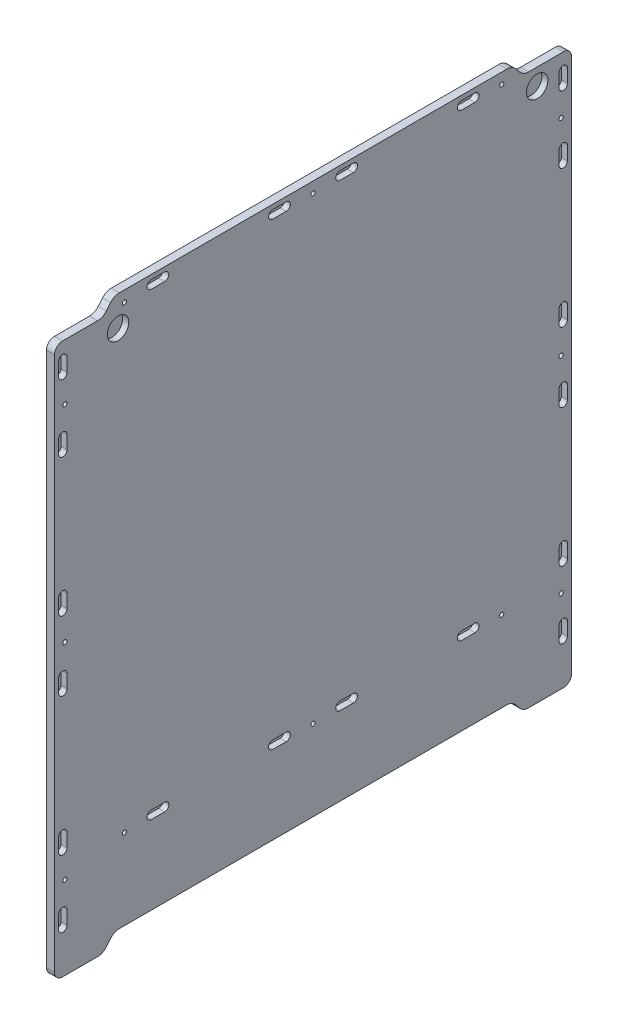
SolidWorks part; units mm, degrees
ref_plane "Alzado" through (0, 0, 0) normal (0, 0, 1) x (1, 0, 0)
ref_plane "Planta" through (0, 0, 0) normal (0, 1, 0) x (1, 0, 0)
ref_plane "Vista lateral" through (0, 0, 0) normal (1, 0, 0) x (0, 0, -1)
sketch "Croquis1" plane through (0, 0, 0) normal (1, 0, 0) x (0, 0, -1)
  line L0 (-15.4032, 213.9092) -> (-15.4032, -196.0905) construction
  line L1 (138.549, -203.0545) -> (135.2533, -199.1268)
  line L2 (171.0968, -206.0908) -> (145.0604, -206.0908)
  line L3 (177.0968, 198.0069) -> (177.0968, -200.0908)
  line L4 (145.0968, 204.0069) -> (171.0968, 204.0069)
  line L5 (-159.667, 213.9092) -> (128.8605, 213.9092)
  line L6 (-166.1784, 210.8729) -> (-169.3918, 207.0432)
  line L7 (-175.9032, 204.0069) -> (-201.9032, 204.0069)
  line L8 (-207.9032, 198.0069) -> (-207.9032, -200.0908)
  line L9 (-201.9032, -206.0908) -> (-175.8668, -206.0908)
  line L10 (-169.3555, -203.0545) -> (-166.0597, -199.1268)
  line L11 (-159.5483, -196.0905) -> (128.7419, -196.0905)
  line L12 (135.3719, 210.8729) -> (138.5854, 207.0432)
  line L21 (-207.9032, 8.9094) -> (177.0968, 8.9094) construction
  arc A0 (128.7419, -196.0905) -> (135.2533, -199.1268) centre (128.7419, -204.5905) cw
  arc A1 (145.0604, -206.0908) -> (138.549, -203.0545) centre (145.0604, -197.5908) cw
  arc A2 (177.0968, -200.0908) -> (171.0968, -206.0908) centre (171.0968, -200.0908) cw
  arc A3 (171.0968, 204.0069) -> (177.0968, 198.0069) centre (171.0968, 198.0069) cw
  arc A4 (145.0968, 204.0069) -> (138.5854, 207.0432) centre (145.0968, 212.5069) cw
  arc A5 (-159.667, 213.9092) -> (-166.1784, 210.8729) centre (-159.667, 205.4092) ccw
  arc A6 (-175.9032, 204.0069) -> (-169.3918, 207.0432) centre (-175.9032, 212.5069) ccw
  arc A7 (-201.9032, 204.0069) -> (-207.9032, 198.0069) centre (-201.9032, 198.0069) ccw
  arc A8 (-207.9032, -200.0908) -> (-201.9032, -206.0908) centre (-201.9032, -200.0908) ccw
  arc A9 (-175.8668, -206.0908) -> (-169.3555, -203.0545) centre (-175.8668, -197.5908) ccw
  arc A10 (-159.5483, -196.0905) -> (-166.0597, -199.1268) centre (-159.5483, -204.5905) ccw
  arc A11 (128.8605, 213.9092) -> (135.3719, 210.8729) centre (128.8605, 205.4092) cw
  circle A12 centre (151.4968, 191.5069) radius 4.25
  circle A13 centre (-160.6032, 191.5069) radius 4.25
  circle A22 centre (-15.4032, 205.9092) radius 1.55
  circle A23 centre (125.0968, 205.9092) radius 1.55
  circle A24 centre (-155.9032, 205.9092) radius 1.55
  circle A25 centre (-15.4032, -136.0908) radius 1.55
  circle A26 centre (125.0968, -136.0908) radius 1.55
  circle A27 centre (-155.9032, -136.0908) radius 1.55
  circle A28 centre (-200.1532, 162.2069) radius 1.6
  circle A29 centre (-200.1532, 8.9094) radius 1.6
  circle A30 centre (-200.1532, -144.3882) radius 1.6
  circle A31 centre (169.3468, -144.3882) radius 1.6
  circle A32 centre (169.3468, 8.9094) radius 1.6
  circle A33 centre (169.3468, 162.2069) radius 1.6
  point P42 (-15.4032, 8.9094)
  dimension "D3" = 15.9023
  dimension "D5" = 385
  dimension "D6" = 25.6
  dimension "D8" = 47.3
  dimension "D4" = 8.5
  dimension "D12" = 41.8
  dimension "D13" = 52
  dimension "D14" = 52
  dimension "D15" = 7.75
  dimension "D16" = 52
  dimension "D17" = 52
  dimension "D22" = 6
  dimension "D23" = 6
  dimension "D25" = 8.5
  dimension "D26" = 8.5
  dimension "D27" = 50
  dimension "D29" = 8.5
  dimension "D30" = 8.5
  dimension "D33" = 3.2
  dimension "D34" = 3.2
  dimension "D18" = 7.75
  dimension "D21" = 10.0003
  dimension "D28" = 32.0364
  dimension "D31" = 32
  dimension "D32" = 50
  dimension "Ancho_panel" = 385
  dimension "Alto_panel" = 420
extrude "Saliente-Extruir1" add sketch "Croquis1" along normal blind 6
sketch "Croquis3" plane through (6, 0, 0) normal (1, 0, 0) x (0, 0, -1)
  line L0 (-15.4032, 213.9092) -> (-15.4032, -196.0905) construction
  line L1 (128.8605, 213.9092) -> (-159.667, 213.9092) construction
  line L2 (-159.5483, -196.0905) -> (128.7419, -196.0905) construction
  line L5 (-198.6032, 192.2069) -> (-198.6032, 182.2069)
  line L6 (-204.8032, 192.2069) -> (-204.8032, 182.2069)
  line L7 (-175.9032, 204.0069) -> (-201.9032, 204.0069) construction
  line L8 (-207.9032, 198.0069) -> (-207.9032, -200.0908) construction
  line L9 (-198.6032, 142.2069) -> (-198.6032, 132.2069)
  line L10 (-204.8032, 142.2069) -> (-204.8032, 132.2069)
  line L11 (177.0968, 8.9094) -> (-207.9032, 8.9094) construction
  line L12 (177.0968, -200.0908) -> (177.0968, 198.0069) construction
  line L13 (-198.6032, -124.3882) -> (-198.6032, -114.3882)
  line L14 (-204.8032, -124.3882) -> (-204.8032, -114.3882)
  line L15 (-204.8032, -174.3882) -> (-204.8032, -164.3882)
  line L16 (-198.6032, -174.3882) -> (-198.6032, -164.3882)
  line L17 (-15.4032, 8.9094) -> (-15.4032, 213.9092) construction
  line L19 (-201.7032, 179.1069) -> (-201.7032, 145.3069) construction
  line L20 (-198.6032, 39.7671) -> (-198.6032, 29.7671)
  line L21 (-204.8032, 39.7671) -> (-204.8032, 29.7671)
  line L22 (-198.6032, -11.9484) -> (-198.6032, -21.9484)
  line L23 (-204.8032, -11.9484) -> (-204.8032, -21.9484)
  line L24 (-201.7032, 26.6671) -> (-201.7032, -8.8484) construction
  line L25 (167.7968, -174.3882) -> (167.7968, -164.3882)
  line L26 (173.9968, -174.3882) -> (173.9968, -164.3882)
  line L27 (173.9968, -124.3882) -> (173.9968, -114.3882)
  line L28 (167.7968, -124.3882) -> (167.7968, -114.3882)
  line L29 (173.9968, -11.9484) -> (173.9968, -21.9484)
  line L30 (167.7968, -11.9484) -> (167.7968, -21.9484)
  line L31 (173.9968, 39.7671) -> (173.9968, 29.7671)
  line L32 (-45.4032, 210.5092) -> (-35.4032, 210.5092)
  line L33 (-45.4032, 204.3092) -> (-35.4032, 204.3092)
  line L34 (-135.9032, 210.5092) -> (-125.9032, 210.5092)
  line L35 (-135.9032, 204.3092) -> (-125.9032, 204.3092)
  line L36 (167.7968, 39.7671) -> (167.7968, 29.7671)
  line L37 (105.0968, 204.3092) -> (95.0968, 204.3092)
  line L38 (105.0968, 210.5092) -> (95.0968, 210.5092)
  line L39 (14.5968, 204.3092) -> (4.5968, 204.3092)
  line L40 (14.5968, 210.5092) -> (4.5968, 210.5092)
  line L41 (-135.9032, -131.4908) -> (-125.9032, -131.4908)
  line L42 (-135.9032, -137.6908) -> (-125.9032, -137.6908)
  line L43 (-45.4032, -131.4908) -> (-35.4032, -131.4908)
  line L44 (-45.4032, -137.6908) -> (-35.4032, -137.6908)
  line L45 (14.5968, -131.4908) -> (4.5968, -131.4908)
  line L46 (14.5968, -137.6908) -> (4.5968, -137.6908)
  line L47 (105.0968, -131.4908) -> (95.0968, -131.4908)
  line L48 (105.0968, -137.6908) -> (95.0968, -137.6908)
  line L49 (-135.9032, 210.5092) -> (-135.9032, -131.4908) construction
  line L50 (173.9968, 142.2069) -> (173.9968, 132.2069)
  line L51 (167.7968, 142.2069) -> (167.7968, 132.2069)
  line L52 (173.9968, 192.2069) -> (173.9968, 182.2069)
  line L53 (167.7968, 192.2069) -> (167.7968, 182.2069)
  circle A0 centre (-160.6032, 191.5069) radius 8
  circle A1 centre (151.4968, 191.5069) radius 8
  arc A4 (-198.6032, 192.2069) -> (-204.8032, 192.2069) centre (-201.7032, 192.2069) ccw
  arc A5 (-204.8032, 182.2069) -> (-198.6032, 182.2069) centre (-201.7032, 182.2069) ccw
  arc A6 (-198.6032, 142.2069) -> (-204.8032, 142.2069) centre (-201.7032, 142.2069) ccw
  arc A7 (-204.8032, 132.2069) -> (-198.6032, 132.2069) centre (-201.7032, 132.2069) ccw
  arc A8 (-204.8032, -114.3882) -> (-198.6032, -114.3882) centre (-201.7032, -114.3882) cw
  arc A9 (-198.6032, -124.3882) -> (-204.8032, -124.3882) centre (-201.7032, -124.3882) cw
  arc A10 (-204.8032, -164.3882) -> (-198.6032, -164.3882) centre (-201.7032, -164.3882) cw
  arc A11 (-198.6032, -174.3882) -> (-204.8032, -174.3882) centre (-201.7032, -174.3882) cw
  arc A12 (-198.6032, 39.7671) -> (-204.8032, 39.7671) centre (-201.7032, 39.7671) ccw
  arc A13 (-204.8032, 29.7671) -> (-198.6032, 29.7671) centre (-201.7032, 29.7671) ccw
  arc A14 (-198.6032, -11.9484) -> (-204.8032, -11.9484) centre (-201.7032, -11.9484) ccw
  arc A15 (-204.8032, -21.9484) -> (-198.6032, -21.9484) centre (-201.7032, -21.9484) ccw
  arc A16 (167.7968, -174.3882) -> (173.9968, -174.3882) centre (170.8968, -174.3882) ccw
  arc A17 (173.9968, -164.3882) -> (167.7968, -164.3882) centre (170.8968, -164.3882) ccw
  arc A18 (167.7968, -124.3882) -> (173.9968, -124.3882) centre (170.8968, -124.3882) ccw
  arc A19 (173.9968, -114.3882) -> (167.7968, -114.3882) centre (170.8968, -114.3882) ccw
  arc A20 (173.9968, -21.9484) -> (167.7968, -21.9484) centre (170.8968, -21.9484) cw
  arc A21 (167.7968, -11.9484) -> (173.9968, -11.9484) centre (170.8968, -11.9484) cw
  arc A22 (173.9968, 29.7671) -> (167.7968, 29.7671) centre (170.8968, 29.7671) cw
  arc A23 (167.7968, 39.7671) -> (173.9968, 39.7671) centre (170.8968, 39.7671) cw
  arc A24 (173.9968, 132.2069) -> (167.7968, 132.2069) centre (170.8968, 132.2069) cw
  arc A25 (167.7968, 142.2069) -> (173.9968, 142.2069) centre (170.8968, 142.2069) cw
  arc A26 (173.9968, 182.2069) -> (167.7968, 182.2069) centre (170.8968, 182.2069) cw
  arc A27 (167.7968, 192.2069) -> (173.9968, 192.2069) centre (170.8968, 192.2069) cw
  arc A28 (-35.4032, 204.3092) -> (-35.4032, 210.5092) centre (-35.4032, 207.4092) ccw
  arc A29 (-45.4032, 210.5092) -> (-45.4032, 204.3092) centre (-45.4032, 207.4092) ccw
  arc A30 (-125.9032, 204.3092) -> (-125.9032, 210.5092) centre (-125.9032, 207.4092) ccw
  arc A31 (-135.9032, 210.5092) -> (-135.9032, 204.3092) centre (-135.9032, 207.4092) ccw
  arc A32 (105.0968, 210.5092) -> (105.0968, 204.3092) centre (105.0968, 207.4092) cw
  arc A33 (95.0968, 204.3092) -> (95.0968, 210.5092) centre (95.0968, 207.4092) cw
  arc A34 (14.5968, 210.5092) -> (14.5968, 204.3092) centre (14.5968, 207.4092) cw
  arc A35 (4.5968, 204.3092) -> (4.5968, 210.5092) centre (4.5968, 207.4092) cw
  arc A36 (-125.9032, -137.6908) -> (-125.9032, -131.4908) centre (-125.9032, -134.5908) ccw
  arc A37 (-135.9032, -131.4908) -> (-135.9032, -137.6908) centre (-135.9032, -134.5908) ccw
  arc A38 (-35.4032, -137.6908) -> (-35.4032, -131.4908) centre (-35.4032, -134.5908) ccw
  arc A39 (-45.4032, -131.4908) -> (-45.4032, -137.6908) centre (-45.4032, -134.5908) ccw
  arc A40 (14.5968, -131.4908) -> (14.5968, -137.6908) centre (14.5968, -134.5908) cw
  arc A41 (4.5968, -137.6908) -> (4.5968, -131.4908) centre (4.5968, -134.5908) cw
  arc A42 (105.0968, -131.4908) -> (105.0968, -137.6908) centre (105.0968, -134.5908) cw
  arc A43 (95.0968, -137.6908) -> (95.0968, -131.4908) centre (95.0968, -134.5908) cw
  circle A44 centre (-155.9032, 205.9092) radius 1.55 construction
  circle A45 centre (-155.9032, 205.9092) radius 1.55 construction
  dimension "D2" = 16
  dimension "D5" = 10
  dimension "D10" = 10
  dimension "D15" = 3.1
  dimension "D17" = 3.1
  dimension "D3" = 16
  dimension "D6" = 11.8
  dimension "D7" = 6.2
  dimension "D11" = 20
  dimension "D12" = 6.5
  dimension "D16" = 20
  dimension "D9" = 10
  dimension "D18" = 6.2
  dimension "D8" = 2
  dimension "D13" = 2
  dimension "D14" = 2
  dimension "Distancia_vert_entre_horizontales_ensambles" = 342
extrude "Cortar-Extruir1" cut sketch "Croquis3" against normal blind 4.5
chamfer "Chaflán1" distance 1.5 angle 45 12 edges at (0, 205.9092, 13.8532) (0, 205.9092, -126.6468) (0, -136.0908, -126.6468) (0, -136.0908, 13.8532) (0, -136.0908, 154.3532) (0, 162.2069, 198.5532) (0, 205.9092, 154.3532) (0, 162.2069, -167.7468) (0, 8.9094, -167.7468) (0, -144.3882, -170.9468) (0, -144.3882, 201.7532) (0, 8.9094, 198.5532)
sketch "Croquis4" plane through (0, 0, 0) normal (-1, 0, 0) x (0, 0, 1)
  line L1 (-146.0451, 197.286) -> (-157.1453, 197.286)
  line L2 (-146.0451, 197.286) -> (-146.0451, 186.0138)
  line L3 (-146.0451, 186.0138) -> (-157.1453, 186.0138)
  line L4 (-157.1453, 197.286) -> (-157.1453, 186.0138)
  line L5 (166.7347, 197.286) -> (154.7354, 197.286)
  line L6 (166.7347, 197.286) -> (166.7347, 186.0138)
  line L7 (166.7347, 186.0138) -> (154.7354, 186.0138)
  line L8 (154.7354, 197.286) -> (154.7354, 186.0138)
extrude "Saliente-Extruir2" add sketch "Croquis4" against normal blind 1.5
equation "\"Ancho_panel\"= 385'Ancho del panel"
equation "\"Alto_panel\"= 420'Alto del panel izquierdo"
equation "\"Altura_base_taladros\"= 70'Alto taladros de la base eje Z"
equation "\"Altura_superior_taladros\"= 8mm'Distancia taladros a top"
equation "\"Distancia_vert_entre_horizontales_ensambles\"= \"Alto_panel\" - \"Altura_base_taladros\" - \"Altura_superior_taladros\"'Distancia vertical entre horizontales de ensambles"
equation "\"Latrales_separacion_barras_a_escalon_bajo\"= 12.5'Separación entre las barras y el escalón inferior de la parte superior"
equation "\"Espacio_tensor_correa_motor\"= 8.5mm'Espacio para mover el motor en vertical y tensar la correa"
